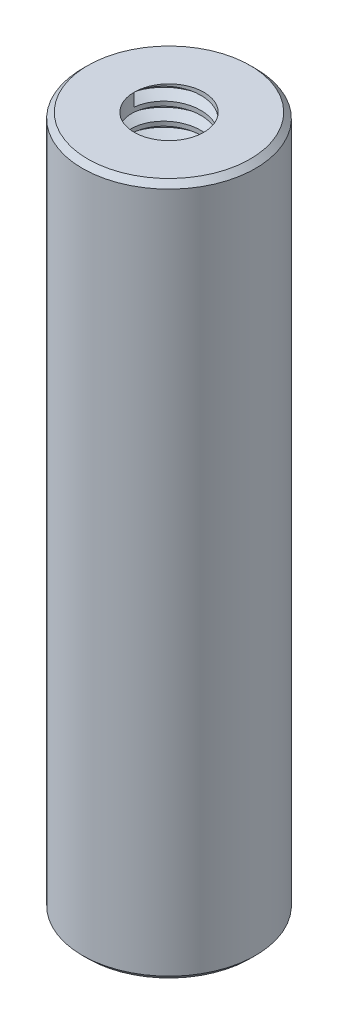
SolidWorks part; units mm, degrees
material "6061-T6 (SS)"
ref_plane "Alzado" through (0, 0, 0) normal (0, 0, 1) x (1, 0, 0)
ref_plane "Planta" through (0, 0, 0) normal (0, 1, 0) x (1, 0, 0)
ref_plane "Vista lateral" through (0, 0, 0) normal (1, 0, 0) x (0, 0, -1)
sketch "Croquis2" plane through (0, 0, 0) normal (0, 1, 0) x (1, 0, 0)
  circle A0 centre (0, 0) radius 6.35
  dimension "D1" = 12.7
extrude "Saliente-Extruir1" add sketch "Croquis2" along normal mid plane 50.8
chamfer "Chaflán1" distance 0.3969 angle 45 2 edges at (0, -25.4, 6.35) (0, 25.4, 6.35)
sketch "Croquis3" plane through (0, 0, 0) normal (0, 1, 0) x (1, 0, 0)
  circle A0 centre (0, 0) radius 2.5527
  dimension "D1" = 5.1054
extrude "Tap Hole 1" cut sketch "Croquis3" against normal blind 19.05 from surface starting at face at (0, 25.4, 5.9531)
extrude "Tap Hole 2" cut sketch "Croquis3<2>" along normal blind 19.05 from surface starting at face at (0, -25.4, 5.9531)
sketch "Croquis3<2>" plane through (0, 0, 0) normal (0, 1, 0) x (1, 0, 0) same geometry as "Croquis3"
sketch "Croquis4" plane through (0, 0, 0) normal (0, 1, 0) x (1, 0, 0)
  circle A0 centre (0, 0) radius 3.2639
  dimension "D1" = 6.5278
extrude "Clearance Hole" [suppressed] cut sketch "Croquis4" against normal through all both and the other way through all
thread "Rosca1" pitch 1.27 method cut profile "Perfil de rosca1" start angle 0, offset 0, length 0, pitch 1.27, diameter 5.1054
ref_plane "Plano1" through (2.5527, -25.4, 0) normal (0, 0, 1) x (1, 0, 0)
sketch "Perfil de rosca1" plane through (2.5527, -25.4, 0) normal (0, 0, 1) x (1, 0, 0)
  line L0 (0, 0) -> (0, 1.27) construction
  line L1 (0, 0) -> (0.6874, 0.3969)
  line L2 (0.6874, 0.3969) -> (0.6874, 0.5556)
  line L3 (0.6874, 0.5556) -> (0, 0.9525)
  line L4 (0.6874, 0.4762) -> (0, 0.4762) construction
  line L11 (0, 0) -> (0, 0.9525)
  point P2 (0, 0)
  dimension "Pitch" = 1.27
  dimension "Profile_Angle" = 60
  dimension "Profile_Land" = 0.1588
  dimension "Profile_Height" = 0.6874
thread "Rosca2" pitch 1.27 method cut profile "Perfil de rosca2" start angle 0, offset 0, length 0, pitch 1.27, diameter 5.1054
ref_plane "Plano2" through (-2.5527, 25.4, 0) normal (0, 0, 1) x (-1, 0, 0)
sketch "Perfil de rosca2" plane through (-2.5527, 25.4, 0) normal (0, 0, 1) x (-1, 0, 0)
  line L0 (0, 0) -> (0, 1.27) construction
  line L1 (0, 0) -> (0.6874, 0.3969)
  line L2 (0.6874, 0.3969) -> (0.6874, 0.5556)
  line L3 (0.6874, 0.5556) -> (0, 0.9525)
  line L4 (0.6874, 0.4762) -> (0, 0.4762) construction
  line L11 (0, 0) -> (0, 0.9525)
  point P2 (0, 0)
  dimension "Pitch" = 1.27
  dimension "Profile_Angle" = 60
  dimension "Profile_Land" = 0.1588
  dimension "Profile_Height" = 0.6874
equation "\"OD\"= 0.5pulgadas"
equation "\"Largo\"= 2pulgadas"
equation "\"Tap Hole\"= IIF ( \"OD\" = 0.375pulgadas , 0.1590pulgadas , 0.201pulgadas )"
equation "\"Spacer Hole\"= IIF ( \"OD\" = 0.375pulgadas , 0.196pulgadas , 0.257pulgadas )"
equation "\"D1@Croquis2\"=\"OD\""
equation "\"D1@Saliente-Extruir1\"=\"Largo\""
equation "\"D1@Croquis3\"=\"Tap Hole\""
equation "\"D1@Croquis4\"=\"Spacer Hole\""
